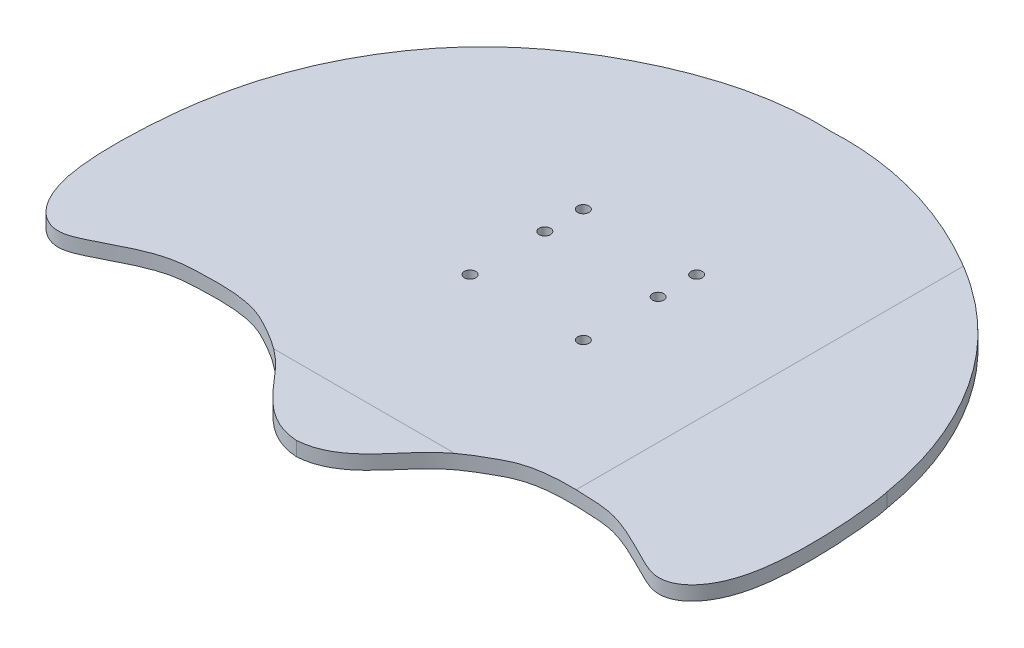
SolidWorks part; units mm, degrees
material "6061-T6 (SS)"
ref_plane "Front Plane" through (0, 0, 0) normal (0, 0, 1) x (1, 0, 0)
ref_plane "Top Plane" through (0, 0, 0) normal (0, 1, 0) x (1, 0, 0)
ref_plane "Right Plane" through (0, 0, 0) normal (1, 0, 0) x (0, 0, -1)
sketch "Sketch3" plane through (0, 0, 0) normal (0, 1, 0) x (1, 0, 0)
  line L0 (0, 0) -> (0, 159.1899) construction
  line L1 (0, 0) -> (0, -140.5301) construction
  line L2 (0, 0) -> (-190.5, 0) construction
  line L3 (0, 0) -> (190.5, 0) construction
  spline S0 degree 3 poles (-190.5, 0) (-184.3927, 37.537) (-157.2613, 93.9641) (-82.3875, 146.6227) (-31.3114, 160.7999) (0, 159.1899) knots 0 0 0 0 0.424401 0.65637 1 1 1 1
  spline S1 degree 3 poles (-190.5, 0) (-192.064, -4.9635) (-201.9672, -83.3146) (-174.6966, -109.29) (-151.6301, -100.568) (-131.4108, -87.7198) (-96.8436, -85.3754) (-78.6925, -86.2588) (-58.8335, -96.8794) (-37.3059, -109.9358) (-21.3496, -139.1148) (0, -140.5301) knots 0 0 0 0 0.166997 0.292321 0.319633 0.426735 0.458914 0.609242 0.64191 0.766802 1 1 1 1
  spline S2 degree 3 poles (190.5, 0) (192.064, -4.9635) (201.9672, -83.3146) (174.6966, -109.29) (151.6301, -100.568) (131.4108, -87.7198) (96.8436, -85.3754) (78.6925, -86.2588) (58.8335, -96.8794) (37.3059, -109.9358) (21.3496, -139.1148) (0, -140.5301) knots 0 0 0 0 0.166997 0.292321 0.319633 0.426735 0.458914 0.609242 0.64191 0.766802 1 1 1 1
  spline S3 degree 3 poles (190.5, 0) (184.3927, 37.537) (157.2613, 93.9641) (82.3875, 146.6227) (31.3114, 160.7999) (0, 159.1899) knots 0 0 0 0 0.424401 0.65637 1 1 1 1
  dimension "D1" = 381
  dimension "D2" = 299.72
  dimension "D3" = 159.1899
  dimension "D4" = 86.8953
  dimension "D5" = 104.4979
  dimension "D6" = 29.1616
  dimension "D7" = 92.2742
  dimension "D8" = 108.411
  dimension "D9" = 67.4883
  dimension "D10" = 43.7314
  dimension "D11" = 117.6915
  dimension "D12" = 162.2568
  dimension "D13" = 89.4522
  dimension "D14" = 140.1036
  dimension "D15" = 175.0666
  dimension "D16" = 50.2669
  dimension "D17" = 101.3666
  dimension "D18" = 138.1225
  dimension "D19" = 155.1557
  dimension "D20" = 192.0074
  dimension "D21" = 193.9268
  dimension "D23" = 76.6666
extrude "Boss-Extrude1" add sketch "Sketch3" along normal blind 7.9502 from surface starting at plane "Top Plane"
sketch "Sketch5" plane through (0, 0, 0) normal (0, -1, 0) x (1, 0, 0)
  line L0 (0, 0) -> (0, -20.32) construction
  line L1 (31.75, -52.07) -> (-31.75, -52.07)
  line L2 (31.75, -52.07) -> (31.75, 11.43)
  line L3 (31.75, 11.43) -> (-31.75, 11.43)
  line L4 (-31.75, -52.07) -> (-31.75, 11.43)
  line L5 (31.75, -52.07) -> (-31.75, 11.43) construction
  line L6 (31.75, 11.43) -> (-31.75, -52.07) construction
  line L7 (-31.75, -52.07) -> (-31.75, -30.48)
  line L8 (-31.75, -30.48) -> (31.75, -30.48) construction
  point P0 (0, -20.32)
  point P3 (0, -20.32)
  dimension "D2" = 63.5
  dimension "D3" = 63.5
  dimension "D4" = 21.59
hole_wizard "1/4 (0.25) Diameter Hole1" positions "Sketch6" profile "Sketch7" hole size "1/4" standard "ANSI Inch" end condition through all
sketch "Sketch6" plane through (0, 0, 0) normal (0, -1, 0) x (-1, 0, 0)
  point P0 (-31.75, 52.07)
  point P3 (31.75, 52.07)
  point P6 (31.75, -11.43)
  point P9 (-31.75, -11.43)
  point P12 (-31.75, 30.48)
  point P15 (31.75, 30.48)
sketch "Sketch7" plane through (31.75, 0, -52.07) normal (1, 0, 0) x (0, 0, -1)
  line L0 (0, 0) -> (0, 7.9502)
  line L1 (0, 7.9502) -> (3.175, 7.9502)
  line L2 (3.175, 7.9502) -> (3.175, 0)
  line L5 (3.175, 0) -> (0, 0)
  line L11 (0, -6.35) -> (0, 107.95) construction
  dimension "Thru Hole Dia." = 6.35
  dimension "Thru Hole Depth" = 7.9502
sketch "Sketch9" plane through (0, 7.9502, 0) normal (0, 1, 0) x (1, 0, 0)
  line L0 (102.3823, -86.0787) -> (102.3823, 130.9193)
  line L1 (-50.7649, -102.4301) -> (50.7649, -102.4301)
  spline S0 degree 3 poles (0, -140.5301) (21.3496, -139.1148) (37.3059, -109.9358) (58.8335, -96.8794) (78.6925, -86.2588) (96.8436, -85.3754) (131.4108, -87.7198) (151.6301, -100.568) (174.6966, -109.29) (201.9672, -83.3146) (192.064, -4.9635) (190.5, 0) knots 0 0 0 0 0.233198 0.35809 0.390758 0.541086 0.573265 0.680367 0.707679 0.833003 1 1 1 1 construction
  spline S1 degree 3 poles (190.5, 0) (184.3927, 37.537) (157.2613, 93.9641) (82.3875, 146.6227) (31.3114, 160.7999) (0, 159.1899) knots 0 0 0 0 0.424401 0.65637 1 1 1 1 construction
  spline S2 degree 3 poles (-190.5, 0) (-192.064, -4.9635) (-201.9672, -83.3146) (-174.6966, -109.29) (-151.6301, -100.568) (-131.4108, -87.7198) (-96.8436, -85.3754) (-78.6925, -86.2588) (-58.8335, -96.8794) (-37.3059, -109.9358) (-21.3496, -139.1148) (0, -140.5301) knots 0 0 0 0 0.166997 0.292321 0.319633 0.426735 0.458914 0.609242 0.64191 0.766802 1 1 1 1 construction
  dimension "D1" = 38.1
split line "Split Line1"
equation "\"Plate thickness\"=0.313"
equation "\"D1@Boss-Extrude1\"=\"Plate thickness\""
equation "\"Bracket Alignment\"= .80"
equation "\"D1@Sketch5\"=\"Bracket Alignment\""
